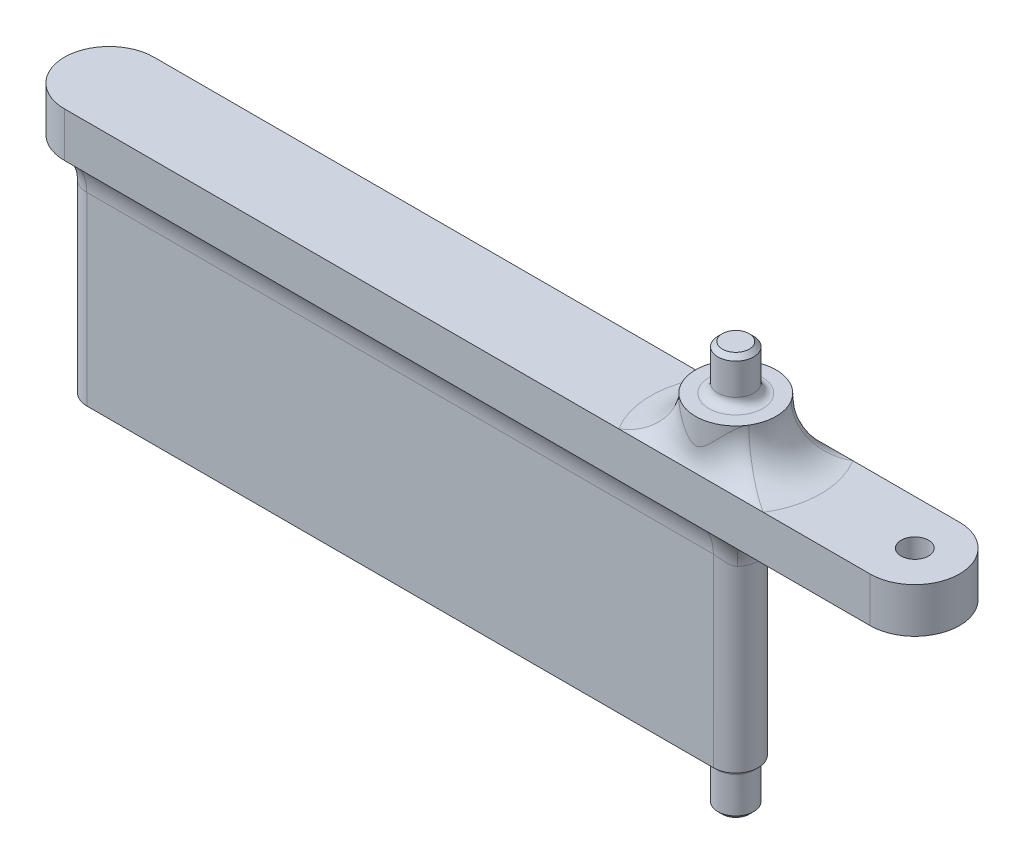
SolidWorks part; units mm, degrees
material "PET"
ref_plane "Front Plane" through (0, 0, 0) normal (0, 0, 1) x (1, 0, 0)
ref_plane "Top Plane" through (0, 0, 0) normal (0, 1, 0) x (1, 0, 0)
ref_plane "Right Plane" through (0, 0, 0) normal (1, 0, 0) x (0, 0, -1)
sketch "Sketch1" plane through (0, 0, 0) normal (0, 1, 0) x (1, 0, 0)
  line L0 (0, 0) -> (-140, 0) construction
  line L1 (0, -5) -> (-140, -5)
  line L2 (0, 5) -> (-140, 5)
  arc A0 (0, -5) -> (0, 5) centre (0, 0) ccw
  arc A1 (-140, 5) -> (-140, -5) centre (-140, 0) ccw
  point P3 (-70, 0)
  dimension "D1" = 140
  dimension "D2" = 10
extrude "Boss-Extrude1" add sketch "Sketch1" against normal blind 50
sketch "Sketch2" plane through (0, 0, 0) normal (0, 1, 0) x (1, 0, 0)
  line L0 (0, 0) -> (-140, 0) construction
  line L5 (-70, -10) -> (-140, -10)
  line L6 (-70, 10) -> (-140, 10)
  line L7 (0, 0) -> (40, 0) construction
  line L8 (-70, 10) -> (40, 10)
  line L9 (-70, -10) -> (40, -10)
  arc A5 (-140, 10) -> (-140, -10) centre (-140, 0) ccw
  arc A7 (40, -10) -> (40, 10) centre (40, 0) ccw
  circle A8 centre (40, 0) radius 3.075
  dimension "D5" = 6.15
  dimension "D7" = 10
  dimension "D1" = 140
  dimension "D2" = 20
  dimension "D3" = 20
  dimension "D4" = 40
  dimension "D6" = 70
extrude "Boss-Extrude2" add sketch "Sketch2" along normal blind 10
fillet "Fillet1" radius 10 3 edges at (5, 0, 0) (-70, 0, -5) (-70, 0, 5)
sketch "Sketch3" plane through (0, 10, 0) normal (0, 1, 0) x (1, 0, 0)
  circle A0 centre (0, 0) radius 9
  dimension "D1" = 18
extrude "Boss-Extrude3" add sketch "Sketch3" along normal blind 10
fillet "Fillet2" radius 10 1 edges at (0, 10, 9)
sketch "Sketch7" plane through (0, -50, 0) normal (0, -1, 0) x (1, 0, 0)
  circle A0 centre (0, 0) radius 4
  dimension "D1" = 8
extrude "Boss-Extrude4" add sketch "Sketch7" along normal blind 10
chamfer "Chamfer1" distance 1 angle 45 1 edges at (0, -60, -4)
sketch "Sketch8" plane through (0, 20, 0) normal (0, 1, 0) x (1, 0, 0)
  circle A1 centre (0, 0) radius 4
  dimension "D1" = 8
extrude "Boss-Extrude5" add sketch "Sketch8" along normal blind 10
chamfer "Chamfer2" distance 1 angle 45 1 edges at (0, 30, 4)
fillet "Fillet4" radius 1 1 edges at (0, -50, 4)
fillet "Fillet5" radius 2 1 edges at (0, 20, 4)
